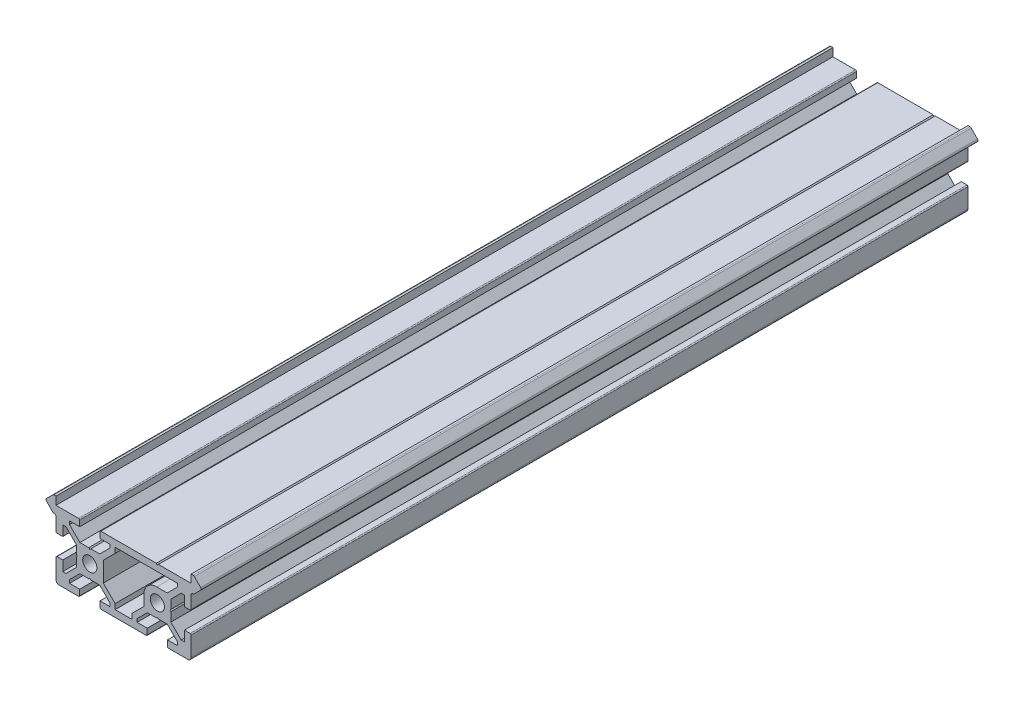
SolidWorks part; units mm, degrees
ref_plane "Front Plane" through (0, 0, 0) normal (0, 0, 1) x (1, 0, 0)
ref_plane "Top Plane" through (0, 0, 0) normal (0, 1, 0) x (1, 0, 0)
ref_plane "Right Plane" through (0, 0, 0) normal (1, 0, 0) x (0, 0, -1)
sketch "Model" plane through (0, 0, 0) normal (0, 0, 1) x (1, 0, 0)
  line L0 (0, 0) -> (0, 76.2) construction
  line L1 (0, 0) -> (101.6, 0) construction
  line L2 (0, 76.2) -> (101.6, 76.2) construction
  line L3 (101.6, 0) -> (101.6, 76.2) construction
  line L4 (28.7715, 48.1056) -> (30.6465, 49.9806)
  line L5 (31.5929, 50.127) -> (31.5929, 47.752)
  line L6 (31.5929, 44.877) -> (31.5929, 41.052)
  line L7 (31.5929, 34.452) -> (31.5929, 28.752)
  line L8 (33.5929, 31.752) -> (33.5929, 34.752)
  line L9 (33.5929, 40.752) -> (33.5929, 43.752)
  line L10 (35.5929, 29.752) -> (35.5929, 30.6914)
  line L11 (35.5929, 44.8127) -> (35.5929, 45.752)
  line L12 (37.5929, 40.6914) -> (37.5929, 38.052)
  line L13 (37.5929, 37.452) -> (37.5929, 34.8127)
  line L14 (38.5929, 28.052) -> (38.5929, 29.752)
  line L15 (38.5929, 45.752) -> (38.5929, 47.452)
  line L16 (32.5929, 27.752) -> (38.2929, 27.752)
  line L17 (44.8929, 27.752) -> (58.2929, 27.752)
  line L18 (64.8929, 27.752) -> (70.5929, 27.752)
  line L19 (37.5929, 38.052) -> (37.8929, 37.752)
  line L20 (41.5929, 34.052) -> (41.8929, 33.752)
  line L21 (30.6465, 45.5235) -> (28.7715, 47.3985)
  line L22 (41.8929, 41.752) -> (41.5929, 41.452)
  line L23 (37.8929, 37.752) -> (37.5929, 37.452)
  line L24 (67.5929, 29.752) -> (64.5929, 29.752)
  line L25 (58.5929, 29.752) -> (55.5929, 29.752)
  line L26 (54.0929, 29.752) -> (49.0929, 29.752)
  line L27 (47.5929, 29.752) -> (44.5929, 29.752)
  line L28 (38.5929, 29.752) -> (35.5929, 29.752)
  line L29 (34.5323, 43.752) -> (37.5929, 40.6914)
  line L30 (44.5323, 33.752) -> (47.5929, 30.6914)
  line L31 (44.5929, 47.452) -> (44.5929, 45.752)
  line L32 (44.5929, 29.752) -> (44.5929, 28.052)
  line L33 (47.5929, 44.8127) -> (44.5323, 41.752)
  line L34 (37.5929, 34.8127) -> (34.5323, 31.752)
  line L35 (69.5929, 31.752) -> (68.6536, 31.752)
  line L36 (34.5323, 31.752) -> (33.5929, 31.752)
  line L37 (49.0929, 31.3127) -> (45.5929, 34.8127)
  line L38 (38.6536, 41.752) -> (35.5929, 44.8127)
  line L39 (45.5929, 34.8127) -> (45.5929, 40.6914)
  line L40 (35.5929, 30.6914) -> (38.6536, 33.752)
  line L41 (45.5929, 40.6914) -> (49.0929, 44.1914)
  line L42 (38.6536, 33.752) -> (41.2929, 33.752)
  line L43 (41.8929, 33.752) -> (44.5323, 33.752)
  line L44 (58.6536, 33.752) -> (61.2929, 33.752)
  line L45 (61.8929, 33.752) -> (64.5323, 33.752)
  line L46 (41.5929, 41.452) -> (41.2929, 41.752)
  line L47 (47.5929, 45.752) -> (47.5929, 44.8127)
  line L48 (47.5929, 30.6914) -> (47.5929, 29.752)
  line L49 (41.2929, 33.752) -> (41.5929, 34.052)
  line L50 (71.2929, 34.752) -> (69.5929, 34.752)
  line L51 (33.5929, 34.752) -> (31.8929, 34.752)
  line L52 (49.0929, 29.752) -> (49.0929, 31.3127)
  line L53 (49.0929, 44.1914) -> (49.0929, 45.752)
  line L54 (61.5929, 47.452) -> (61.8929, 47.752)
  line L55 (31.8929, 40.752) -> (33.5929, 40.752)
  line L56 (69.5929, 40.752) -> (71.2929, 40.752)
  line L57 (54.0929, 31.3127) -> (54.0929, 29.752)
  line L58 (64.5323, 41.752) -> (61.4029, 41.752)
  line L59 (44.5323, 41.752) -> (41.8929, 41.752)
  line L60 (41.2929, 41.752) -> (38.6536, 41.752)
  line L61 (61.5929, 34.052) -> (61.8929, 33.752)
  line L62 (55.5929, 29.752) -> (55.5929, 30.6914)
  line L63 (33.5929, 43.752) -> (34.5323, 43.752)
  line L64 (68.6536, 43.752) -> (69.5929, 43.752)
  line L65 (57.5929, 37.942) -> (57.5929, 34.8127)
  line L66 (58.5929, 28.052) -> (58.5929, 29.752)
  line L67 (31.0929, 45.377) -> (31, 45.377)
  line L68 (72.0929, 45.377) -> (72.1858, 45.377)
  line L69 (35.5929, 45.752) -> (38.5929, 45.752)
  line L70 (44.5929, 45.752) -> (47.5929, 45.752)
  line L71 (49.0929, 45.752) -> (67.5929, 45.752)
  line L72 (64.5323, 33.752) -> (67.5929, 30.6914)
  line L73 (68.6536, 31.752) -> (65.5929, 34.8127)
  line L74 (67.5929, 44.8127) -> (64.5323, 41.752)
  line L75 (57.5929, 34.8127) -> (54.0929, 31.3127)
  line L76 (55.5929, 30.6914) -> (58.6536, 33.752)
  line L77 (65.5929, 40.6914) -> (68.6536, 43.752)
  line L78 (72.5394, 45.5235) -> (74.4144, 47.3985)
  line L79 (71.5929, 47.752) -> (61.8929, 47.752)
  line L80 (61.2929, 47.752) -> (44.8929, 47.752)
  line L81 (38.2929, 47.752) -> (31.5929, 47.752)
  line L82 (65.5929, 37.452) -> (65.2929, 37.752)
  line L83 (61.2929, 33.752) -> (61.5929, 34.052)
  line L84 (65.2929, 37.752) -> (65.5929, 38.052)
  line L85 (72.1858, 50.127) -> (71.5929, 50.127)
  line L86 (31, 50.127) -> (31.5929, 50.127)
  line L87 (64.5929, 29.752) -> (64.5929, 28.052)
  line L88 (61.2929, 47.752) -> (61.5929, 47.452)
  line L89 (65.5929, 34.8127) -> (65.5929, 37.452)
  line L90 (65.5929, 38.052) -> (65.5929, 40.6914)
  line L91 (67.5929, 45.752) -> (67.5929, 44.8127)
  line L92 (67.5929, 30.6914) -> (67.5929, 29.752)
  line L93 (69.5929, 43.752) -> (69.5929, 40.752)
  line L94 (69.5929, 34.752) -> (69.5929, 31.752)
  line L95 (71.5929, 50.127) -> (71.5929, 47.752)
  line L96 (71.5929, 28.752) -> (71.5929, 34.452)
  line L97 (71.5929, 41.052) -> (71.5929, 44.877)
  line L98 (74.4144, 48.1056) -> (72.5394, 49.9806)
  arc A0 (61.4029, 41.752) -> (57.5929, 37.942) centre (61.4029, 37.942) ccw
  circle A1 centre (61.5929, 37.752) radius 2.1
  circle A2 centre (41.5929, 37.752) radius 2.1
  arc A3 (31.5929, 28.752) -> (32.5929, 27.752) centre (32.5929, 28.752) ccw
  arc A4 (70.5929, 27.752) -> (71.5929, 28.752) centre (70.5929, 28.752) ccw
  arc A5 (31.5929, 44.877) -> (31.0929, 45.377) centre (31.0929, 44.877) ccw
  arc A6 (72.0929, 45.377) -> (71.5929, 44.877) centre (72.0929, 44.877) ccw
  arc A7 (31, 50.127) -> (30.6465, 49.9806) centre (31, 49.627) ccw
  arc A8 (28.7715, 48.1056) -> (28.7715, 47.3985) centre (29.125, 47.752) ccw
  arc A9 (30.6465, 45.5235) -> (31, 45.377) centre (31, 45.877) ccw
  arc A10 (72.5394, 49.9806) -> (72.1858, 50.127) centre (72.1858, 49.627) ccw
  arc A11 (74.4144, 47.3985) -> (74.4144, 48.1056) centre (74.0608, 47.752) ccw
  arc A12 (72.1858, 45.377) -> (72.5394, 45.5235) centre (72.1858, 45.877) ccw
  arc A13 (31.8929, 34.752) -> (31.5929, 34.452) centre (31.8929, 34.452) ccw
  arc A14 (44.8929, 47.752) -> (44.5929, 47.452) centre (44.8929, 47.452) ccw
  arc A15 (38.5929, 47.452) -> (38.2929, 47.752) centre (38.2929, 47.452) ccw
  arc A16 (31.5929, 41.052) -> (31.8929, 40.752) centre (31.8929, 41.052) ccw
  arc A17 (38.2929, 27.752) -> (38.5929, 28.052) centre (38.2929, 28.052) ccw
  arc A18 (44.5929, 28.052) -> (44.8929, 27.752) centre (44.8929, 28.052) ccw
  arc A19 (58.2929, 27.752) -> (58.5929, 28.052) centre (58.2929, 28.052) ccw
  arc A20 (64.5929, 28.052) -> (64.8929, 27.752) centre (64.8929, 28.052) ccw
  arc A21 (71.5929, 34.452) -> (71.2929, 34.752) centre (71.2929, 34.452) ccw
  arc A22 (71.2929, 40.752) -> (71.5929, 41.052) centre (71.2929, 41.052) ccw
extrude "Boss-Extrude1" add sketch "Model" along normal blind 230
ref_plane "Plane1" through (51.5929, 0, 0) normal (-1, 0, 0) x (0, 0, 1)
